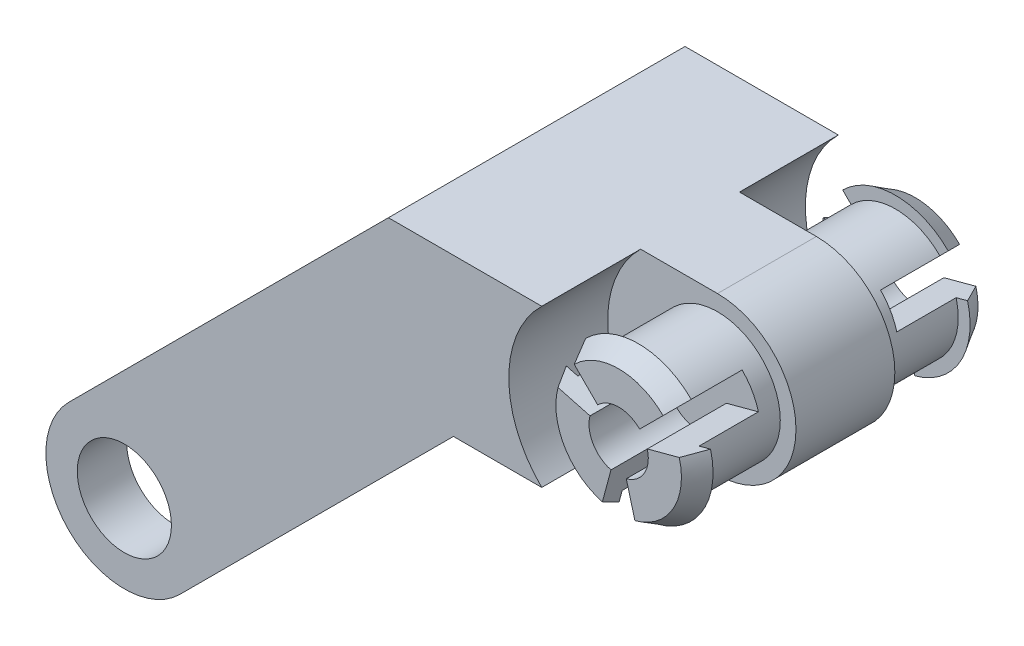
SolidWorks part; units mm, degrees
ref_plane "Alzado" through (0, 0, 0) normal (0, 0, 1) x (1, 0, 0)
ref_plane "Planta" through (0, 0, 0) normal (0, 1, 0) x (1, 0, 0)
ref_plane "Vista lateral" through (0, 0, 0) normal (1, 0, 0) x (0, 0, -1)
sketch "Croquis1" plane through (0, 0, 0) normal (0, 0, 1) x (1, 0, 0)
  line L0 (-2.8063, 2.8063) -> (13.3561, 18.9688)
  line L1 (13.3561, 18.9688) -> (25, 18.9688)
  line L2 (25, 18.9688) -> (25, 11.0312)
  line L3 (25, 11.0312) -> (16.6439, 11.0312)
  line L4 (16.6439, 11.0312) -> (2.8063, -2.8063)
  line L5 (0, -3.9687) -> (16.1518, -3.9687) construction
  line L6 (0, 0) -> (0, 22.779) construction
  line L7 (18.0887, 15) -> (31.0225, 15) construction
  line L8 (-11.9933, 0) -> (35.7455, 0) construction
  circle A0 centre (0, 0) radius 3.9687
  circle A1 centre (25, 15) radius 3.9688
  dimension "D1" = 7.9375
  dimension "D3" = 25
  dimension "D2" = 45
  dimension "D4" = 15
extrude "Saliente-Extruir1" add sketch "Croquis1" along normal mid plane 15 contours A0 | A1 L1 L0 A0 L4 L3 | L2 A1 | L2 A1 region at (11.251, 10.5153, 0) region at (0, 0, 0) region at (26.6844, 15, 0) region at (23.3156, 15, 0)
sketch "Croquis2" plane through (-2.8063, 2.8063, 0) normal (-0.7071, 0.7071, 0) x (0, 0, 1)
  line L0 (0, 3.5718) -> (0, -6.6545) construction
  line L1 (-7.5, 0) -> (7.5, 0) construction
  line L2 (-7.5, 0) -> (-7.5, -3.9688) construction
  line L3 (-7.5, -3.9688) -> (7.5, -3.9688) construction
  line L4 (7.5, 0) -> (7.5, -3.9688) construction
  line L5 (-5, 0) -> (-2.5, 0)
  line L6 (-5, 0) -> (-5, -3.9688)
  line L7 (-5, -3.9688) -> (-2.5, -3.9688)
  line L8 (-2.5, 0) -> (-2.5, -3.9688)
  line L9 (5, -3.9688) -> (2.5, -3.9688)
  line L10 (2.5, 0) -> (2.5, -3.9688)
  line L11 (5, 0) -> (2.5, 0)
  line L12 (5, 0) -> (5, -3.9688)
  dimension "D1" = 2.5
  dimension "D2" = 5
extrude "Cortar-Extruir1" cut sketch "Croquis2" against normal blind 15
sketch "Croquis4" plane through (0, 0, 7.5) normal (0, 0, 1) x (1, 0, 0)
  circle A0 centre (0, 0) radius 2.3813
  dimension "D1" = 4.7625
extrude "Cortar-Extruir2" cut sketch "Croquis4" against normal blind 15
sketch "Croquis5" plane through (0, 0, 7.5) normal (0, 0, 1) x (1, 0, 0)
  circle A0 centre (25, 15) radius 5.5562
  dimension "D1" = 11.1125
extrude "Cortar-Extruir3" cut sketch "Croquis5" against normal blind 5
mirror "Simetría1" about plane through (0, 0, 0) normal (0, 0, 1) of "Cortar-Extruir3"
sketch "Croquis7" plane through (0, 0, -2.5) normal (0, 0, -1) x (-1, 0, 0)
  circle A0 centre (-25, 15) radius 0.5
  dimension "D1" = 1
ref_plane "Plano1" through (25, 0, 0) normal (1, 0, 0) x (0, 0, -1)
sketch "Croquis8" plane through (25, 0, 0) normal (1, 0, 0) x (0, 0, -1)
  line L0 (2.5, 15) -> (4.5, 15) construction
  line L1 (2.5, 14.5) -> (2.5, 15.5) construction
  line L2 (2.5, 11.0312) -> (2.5, 18.9688) construction
  line L3 (2.5, 11.825) -> (7.5, 11.825) construction
  line L4 (2.5, 11.825) -> (2.5, 18.175) construction
  line L5 (2.5, 18.175) -> (7.5, 18.175) construction
  line L6 (7.5, 11.825) -> (7.5, 18.175) construction
  line L7 (2.5, 16.5) -> (7.5, 16.5)
  line L8 (2.5, 16.5) -> (2.5, 18.175)
  line L9 (2.5, 18.175) -> (6.5, 18.175)
  line L10 (6.5, 18.175) -> (6.5, 18.775)
  line L11 (6.5, 18.775) -> (7.5, 18.175)
  line L12 (7.5, 18.175) -> (7.5, 16.5)
  line L13 (3.5, 16.5) -> (3.5, 15)
  line L14 (3.5, 15) -> (2.5, 15)
  line L15 (2.5, 15) -> (2.5, 16.5)
  line L16 (3.5, 16.5) -> (2.5, 16.5)
  point P10 (7.5, 15)
  dimension "D1" = 5
  dimension "D2" = 6.35
  dimension "D3" = 0.6
  dimension "D4" = 1.5
  dimension "D5" = 1
  dimension "D6" = 1
revolve "Revolución1" add sketch "Croquis8" angle 360 about L0 region at (25, 17.3734, -5.0634) region at (25, 15.75, -3)
sketch "Croquis9" plane through (0, 0, -7.5) normal (0, 0, -1) x (-1, 0, 0)
  line L0 (-25, 15) -> (-25, 10.225) construction
  line L3 (-25, 15) -> (-26.2359, 10.3877)
  line L4 (-25, 15) -> (-23.7641, 10.3877)
  line L5 (-25, 15) -> (-29.6123, 16.2359)
  line L6 (-25, 15) -> (-28.3764, 18.3764)
  line L7 (-25, 15) -> (-21.6236, 18.3764)
  line L8 (-25, 15) -> (-20.3877, 16.2359)
  arc A1 (-28.3764, 18.3764) -> (-29.6123, 16.2359) centre (-25, 15) ccw
  arc A4 (-20.3877, 16.2359) -> (-21.6236, 18.3764) centre (-25, 15) ccw
  circle A6 centre (-25, 15) radius 4.775
  arc A7 (-26.2359, 10.3877) -> (-23.7641, 10.3877) centre (-25, 15) ccw
  point P10 (-25, 15)
  dimension "D3" = 1
  dimension "D2" = 3
  dimension "D1" = 15
extrude "Cortar-Extruir6" cut sketch "Croquis9" against normal blind 4 contours L6 A1 L5 L8 | L5 A1 L6 | L8 A4 L7 | L3 A7 L4 region at (27.7255, 16.5735, -7.5)
mirror "Simetría2" about plane through (0, 0, 0) normal (0, 0, 1) of "Cortar-Extruir6", "Revolución1"
